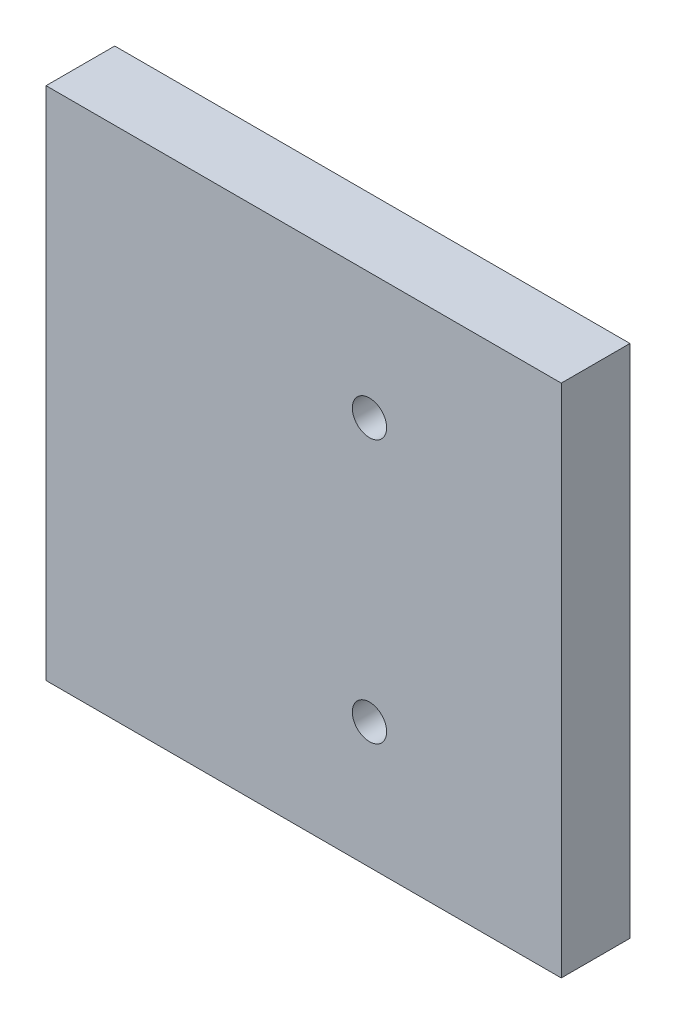
SolidWorks part; units mm, degrees
ref_plane "Front Plane" through (0, 0, 0) normal (0, 0, 1) x (1, 0, 0)
ref_plane "Top Plane" through (0, 0, 0) normal (0, 1, 0) x (1, 0, 0)
ref_plane "Right Plane" through (0, 0, 0) normal (1, 0, 0) x (0, 0, -1)
sketch "Sketch1" plane through (0, 0, 0) normal (0, 0, 1) x (1, 0, 0)
  line L1 (0, 0) -> (45, 0)
  line L2 (0, 0) -> (0, 45)
  line L3 (0, 45) -> (45, 45)
  line L4 (45, 0) -> (45, 45)
  dimension "D1" = 45
  dimension "D2" = 45
extrude "Boss-Extrude1" add sketch "Sketch1" along normal blind 6
extrude "Cut-Extrude1" cut sketch "Sketch2" against normal blind 7.5 and the other way through all
sketch "Sketch2" plane through (62.4346, 22.5, -36.4959) normal (0, 0, 1) x (0, 1, 0)
  circle A0 centre (11.5, 34.1846) radius 1.5
  circle A1 centre (-11.5, 34.1846) radius 1.5
